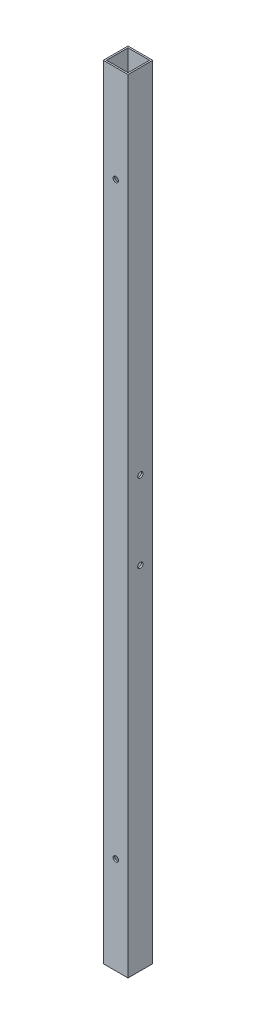
SolidWorks part; units mm, degrees
ref_plane "Front Plane" through (0, 0, 0) normal (0, 0, 1) x (1, 0, 0)
ref_plane "Top Plane" through (0, 0, 0) normal (0, 1, 0) x (1, 0, 0)
ref_plane "Right Plane" through (0, 0, 0) normal (1, 0, 0) x (0, 0, -1)
sketch "Sketch1" plane through (0, 0, 0) normal (0, 1, 0) x (1, 0, 0)
  line L0 (-6.9, -6.9) -> (-6.9, 6.9)
  line L1 (-7.9, -7.9) -> (7.9, -7.9)
  line L2 (-7.9, -7.9) -> (-7.9, 7.9)
  line L3 (-7.9, 7.9) -> (7.9, 7.9)
  line L4 (7.9, -7.9) -> (7.9, 7.9)
  line L5 (-7.9, -7.9) -> (7.9, 7.9) construction
  line L6 (-7.9, 7.9) -> (7.9, -7.9) construction
  line L7 (-6.9, 6.9) -> (6.9, 6.9)
  line L8 (6.9, -6.9) -> (6.9, 6.9)
  line L9 (-6.9, -6.9) -> (6.9, -6.9)
  point P0 (0, 0)
  dimension "D1" = 1
extrude "Boss-Extrude2" add sketch "Sketch1" along normal blind 500
sketch "Sketch4" plane through (0, 0, -7.9) normal (0, 0, -1) x (-1, 0, 0)
  circle A1 centre (-0.0943, 438) radius 1.7
  circle A2 centre (-0.0943, 62) radius 1.7
  point P0 (0, 0)
  dimension "D1" = 376
  dimension "D4" = 3.4
extrude "Cut-Extrude2" cut sketch "Sketch4" against normal through all
sketch "Sketch6" plane through (7.9, 0, 0) normal (1, 0, 0) x (0, 0, -1)
  circle A0 centre (0, 274.4407) radius 1.7
  circle A1 centre (0, 224.4407) radius 1.7
  point P8 (0, 224.4407)
  dimension "D1" = 3.4
  dimension "D2" = 50
extrude "Cut-Extrude3" cut sketch "Sketch6" against normal through all
